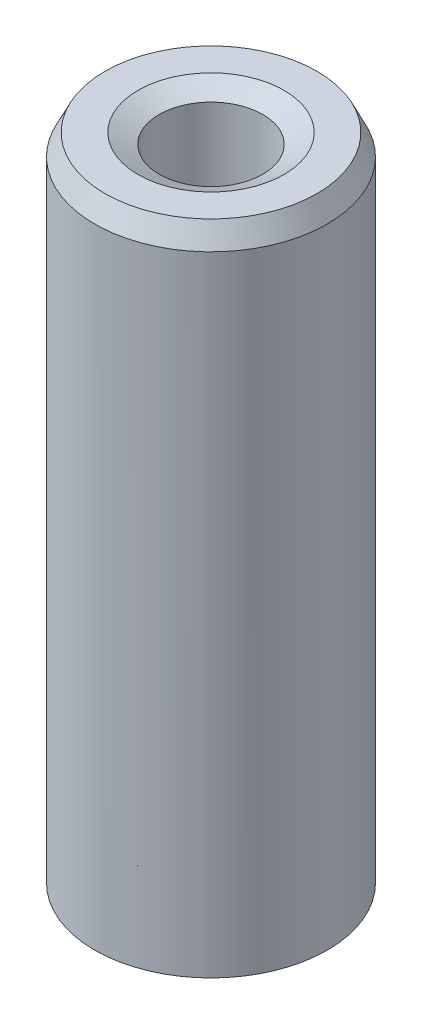
SolidWorks part; units mm, degrees
ref_plane "Front Plane" through (0, 0, 0) normal (0, 0, 1) x (1, 0, 0)
ref_plane "Top Plane" through (0, 0, 0) normal (0, 1, 0) x (1, 0, 0)
ref_plane "Right Plane" through (0, 0, 0) normal (1, 0, 0) x (0, 0, -1)
sketch "Sketch1" plane through (0, 0, 0) normal (0, 1, 0) x (1, 0, 0)
  circle A0 centre (0, 0) radius 5
  dimension "SLEEVE_OD" = 10
extrude "Boss-Extrude1" add sketch "Sketch1" along normal blind 28.3823
sketch "Sketch2" plane through (0, 0, 0) normal (0, 1, 0) x (1, 0, 0)
  circle A0 centre (0, 0) radius 2.2264
  dimension "BORE_D" = 4.4529
extrude "Cut-Extrude1" cut sketch "Sketch2" along normal through all
chamfer "Chamfer1" distance 0.9106 angle 26.014 4 edges at (0, 28.3823, 2.2264) (0, 0, 2.2264) (0, 0, 5) (0, 28.3823, 5) first distance on face at (0, 28.3823, 2.2264) first distance on face at (0, 0, 2.2264) first distance on face at (0, 28.3823, 5)
